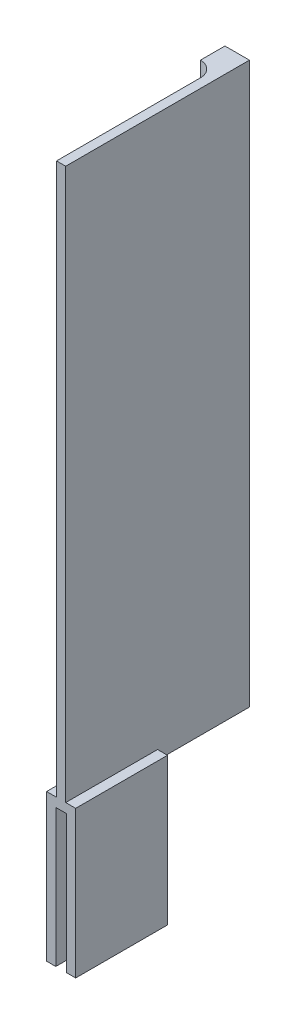
SolidWorks part; units mm, degrees
ref_plane "前视基准面" through (0, 0, 0) normal (0, 0, 1) x (1, 0, 0)
ref_plane "上视基准面" through (0, 0, 0) normal (0, 1, 0) x (1, 0, 0)
ref_plane "右视基准面" through (0, 0, 0) normal (1, 0, 0) x (0, 0, -1)
sketch "草图1" plane through (0, 0, 0) normal (0, 0, 1) x (1, 0, 0)
  line L1 (0, 0) -> (3, 0)
  line L2 (0, 0) -> (0, 45)
  line L3 (0, 45) -> (3, 45)
  line L4 (3, 0) -> (3, 45)
  line L5 (6.5, 0) -> (9.5, 0)
  line L6 (6.5, 0) -> (6.5, 45)
  line L7 (6.5, 45) -> (9.5, 45)
  line L8 (9.5, 0) -> (9.5, 45)
  dimension "D1" = 3
  dimension "D2" = 45
  dimension "D3" = 3
  dimension "D4" = 3.5
  dimension "D5" = 45
extrude "凸台-拉伸1" add sketch "草图1" along normal blind 30
sketch "草图2" plane through (0, 45, 0) normal (0, 1, 0) x (1, 0, 0)
  line L1 (0, 0) -> (9.5, 0)
  line L2 (0, 0) -> (0, -30)
  line L3 (0, -30) -> (9.5, -30)
  line L4 (9.5, 0) -> (9.5, -30)
extrude "凸台-拉伸2" add sketch "草图2" along normal blind 3
sketch "草图3" plane through (0, 48, 0) normal (0, 1, 0) x (1, 0, 0)
  line L0 (4.75, 0) -> (4.75, -30) construction
  line L1 (3.25, 30) -> (6.25, 30)
  line L2 (3.25, 30) -> (3.25, -30)
  line L3 (3.25, -30) -> (6.25, -30)
  line L4 (6.25, 30) -> (6.25, -30)
  line L5 (9.5, 0) -> (0, 0) construction
  line L6 (0, -30) -> (9.5, -30) construction
  line L8 (4.75, 30) -> (4.75, -30) construction
  dimension "D1" = 60
  dimension "D2" = 3
extrude "凸台-拉伸3" add sketch "草图3" along normal blind 180 contours L2 L3 L4 L1
sketch "草图4" plane through (0, 228, 0) normal (0, 1, 0) x (1, 0, 0)
  line L1 (-1.75, 22) -> (3.25, 22)
  line L2 (-1.75, 22) -> (-1.75, 30)
  line L3 (-1.75, 30) -> (3.25, 30)
  line L4 (3.25, 22) -> (3.25, 30)
  dimension "D1" = 5
  dimension "D2" = 8
extrude "凸台-拉伸4" add sketch "草图4" against normal up to surface (180 mm away) up to face at (7.875, 48, 15)
fillet "圆角4" radius 5 1 edges at (3.25, 138, -22)
sketch "草图5" plane through (0, 48, 0) normal (0, -1, 0) x (1, 0, 0)
  line L5 (6.25, -30) -> (6.25, 0)
  line L6 (6.25, 0) -> (3.25, 0)
  line L7 (3.25, 0) -> (3.25, -17)
  line L8 (-1.75, -22) -> (-1.75, -30)
  line L9 (-1.75, -30) -> (6.25, -30)
  line L10 (6.25, -30) -> (6.25, 0)
  line L11 (6.25, 0) -> (3.25, 0)
  line L12 (3.25, 0) -> (3.25, -17)
  line L13 (-1.75, -22) -> (-1.75, -30)
  line L14 (-1.75, -30) -> (6.25, -30)
  arc A1 (-1.75, -22) -> (3.25, -17) centre (-1.75, -17) ccw
  arc A2 (-1.75, -22) -> (3.25, -17) centre (-1.75, -17) ccw
  dimension "D1" = 0
extrude "凸台-拉伸5" add sketch "草图5" along normal up to surface (3 mm away) up to face at (4.75, 45, 15)
